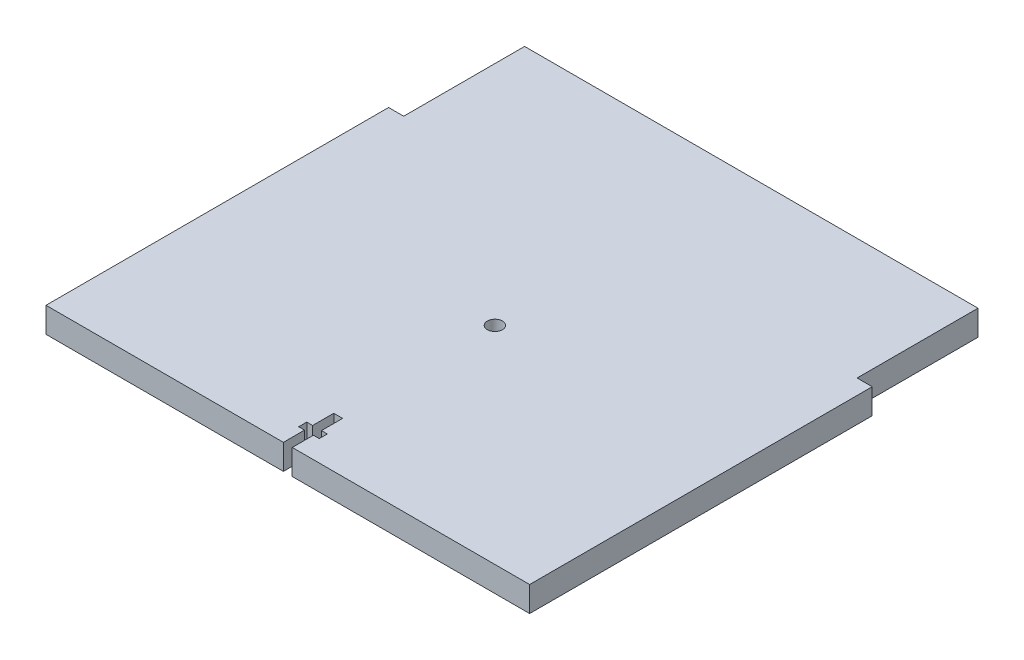
SolidWorks part; units mm, degrees
ref_plane "Front Plane" through (0, 0, 0) normal (0, 0, 1) x (1, 0, 0)
ref_plane "Top Plane" through (0, 0, 0) normal (0, 1, 0) x (1, 0, 0)
ref_plane "Right Plane" through (0, 0, 0) normal (1, 0, 0) x (0, 0, -1)
sketch "Sketch1" plane through (0, 0, 0) normal (0, 1, 0) x (1, 0, 0)
  line L1 (0, 0) -> (142.875, 0)
  line L2 (0, 107.95) -> (0, 146.05)
  line L3 (0, 146.05) -> (142.875, 146.05)
  line L4 (142.875, 107.95) -> (142.875, 146.05)
  line L5 (142.875, 0) -> (147.6375, 0)
  line L7 (142.875, 107.95) -> (147.6375, 107.95)
  line L8 (147.6375, 0) -> (147.6375, 107.95)
  line L9 (0, 0) -> (-4.7625, 0)
  line L11 (0, 107.95) -> (-4.7625, 107.95)
  line L12 (-4.7625, 0) -> (-4.7625, 107.95)
  dimension "D1" = 142.875
  dimension "D2" = 146.05
  dimension "D3" = 4.7625
  dimension "D4" = 4.7625
  dimension "D5" = 107.95
  dimension "D6" = 107.95
extrude "Boss-Extrude1" add sketch "Sketch1" along normal blind 7.9375
sketch "Sketch10" plane through (0, 7.9375, 0) normal (0, 1, 0) x (1, 0, 0)
  line L0 (71.4375, 146.05) -> (71.4375, 15.875) construction
  line L1 (70.0405, 9.2075) -> (68.199, 9.2075)
  line L3 (142.875, 146.05) -> (0, 146.05) construction
  line L4 (-4.7625, 0) -> (147.6375, 0) construction
  line L5 (70.0405, 6.6675) -> (70.0405, 0)
  line L6 (70.0405, 15.875) -> (72.8345, 15.875)
  line L7 (70.0405, 15.875) -> (70.0405, 9.2075)
  line L8 (70.0405, 0) -> (72.8345, 0)
  line L9 (72.8345, 15.875) -> (72.8345, 9.2075)
  line L12 (74.676, 6.6675) -> (72.8345, 6.6675)
  line L13 (74.676, 6.6675) -> (74.676, 9.2075)
  line L14 (74.676, 9.2075) -> (72.8345, 9.2075)
  line L15 (68.199, 6.6675) -> (68.199, 9.2075)
  line L18 (70.0405, 6.6675) -> (68.199, 6.6675)
  line L26 (72.8345, 6.6675) -> (72.8345, 0)
  point P6 (71.4375, 7.9375)
  point P11 (71.4375, 7.9375)
  dimension "D1" = 2.794
  dimension "D2" = 15.875
  dimension "D3" = 2.54
  dimension "D4" = 6.477
extrude "Cut-Extrude2" cut sketch "Sketch10" against normal through all
hole_wizard "3/16 (0.1875) Diameter Hole1" positions "Sketch11" profile "Sketch13" hole size "3/16" standard "ANSI Inch" end condition through all
sketch "Sketch11" plane through (0, 0, 0) normal (0, -1, 0) x (-1, 0, 0)
  line L0 (-142.875, -6.1905) -> (0, 136.6845) construction
  line L1 (0, 146.05) -> (0, 107.95) construction
  line L2 (-142.875, 136.6845) -> (-142.875, 109.57) construction
  line L3 (-142.875, -6.1905) -> (-147.6375, -6.1905) construction
  line L4 (4.7625, 136.6845) -> (-147.6375, 136.6845) construction
  point P7 (-71.4375, 65.247)
sketch "Sketch13" plane through (71.4375, 0, -65.247) normal (1, 0, 0) x (0, 0, -1)
  line L0 (0, 0) -> (0, 7.9375)
  line L1 (0, 7.9375) -> (2.3812, 7.9375)
  line L2 (2.3812, 7.9375) -> (2.3812, 0)
  line L5 (2.3812, 0) -> (0, 0)
  line L11 (0, -6.35) -> (0, 107.95) construction
  dimension "Thru Hole Dia." = 4.7625
  dimension "Thru Hole Depth" = 7.9375
